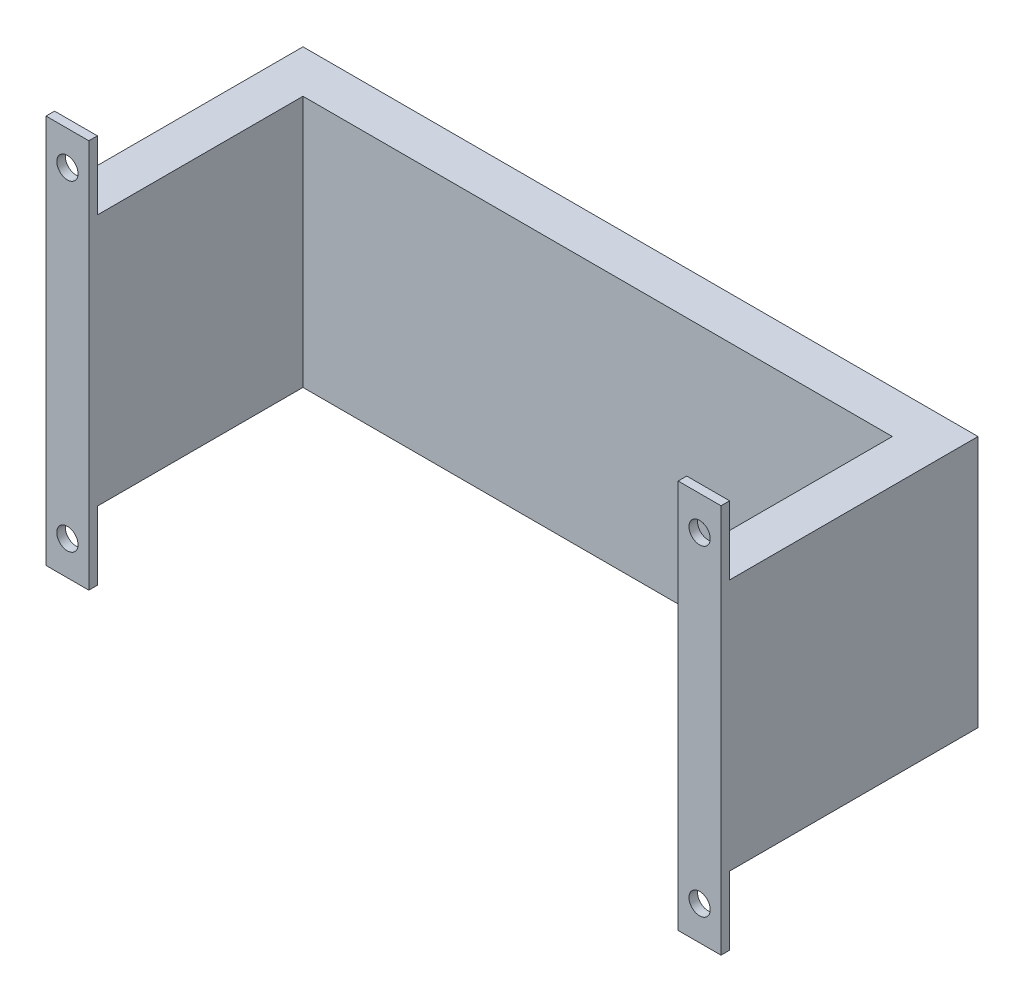
SolidWorks part; units mm, degrees
material "1060 Alloy"
ref_plane "Front Plane" through (0, 0, 0) normal (0, 0, 1) x (1, 0, 0)
ref_plane "Top Plane" through (0, 0, 0) normal (0, 1, 0) x (1, 0, 0)
ref_plane "Right Plane" through (0, 0, 0) normal (1, 0, 0) x (0, 0, -1)
sketch "Sketch1" plane through (0, 0, 0) normal (0, 0, 1) x (1, 0, 0)
  line L1 (125.095, -46.736) -> (-125.095, -46.736)
  line L2 (125.095, -46.736) -> (125.095, 46.736)
  line L3 (125.095, 46.736) -> (-125.095, 46.736)
  line L4 (-125.095, -46.736) -> (-125.095, 46.736)
  line L5 (125.095, -46.736) -> (-125.095, 46.736) construction
  line L6 (125.095, 46.736) -> (-125.095, -46.736) construction
  point P0 (0, 0)
  dimension "D1" = 93.472
  dimension "D2" = 250.19
extrude "Boss-Extrude1" add sketch "Sketch1" along normal blind 95.25
sketch "Sketch5" plane through (0, 0, 95.25) normal (0, 0, 1) x (1, 0, 0)
  line L1 (109.22, -46.736) -> (-109.22, -46.736)
  line L2 (109.22, -46.736) -> (109.22, 46.736)
  line L3 (109.22, 46.736) -> (-109.22, 46.736)
  line L4 (-109.22, -46.736) -> (-109.22, 46.736)
  line L5 (109.22, -46.736) -> (-109.22, 46.736) construction
  line L6 (109.22, 46.736) -> (-109.22, -46.736) construction
  point P0 (0, 0)
  dimension "D1" = 93.472
  dimension "D2" = 218.44
extrude "Cut-Extrude1" cut sketch "Sketch5" against normal blind 79.375
sketch "Sketch6" plane through (0, 0, 95.25) normal (0, 0, 1) x (1, 0, 0)
  line L1 (109.22, 72.136) -> (125.095, 72.136)
  line L2 (109.22, 72.136) -> (109.22, 46.736)
  line L3 (109.22, 46.736) -> (125.095, 46.736)
  line L4 (125.095, 72.136) -> (125.095, 46.736)
  line L5 (109.22, 72.136) -> (125.095, 46.736) construction
  line L6 (109.22, 46.736) -> (125.095, 72.136) construction
  line L8 (125.095, 46.736) -> (109.22, 46.736) construction
  line L9 (125.095, -46.736) -> (125.095, 46.736) construction
  line L11 (0, -51.4096) -> (0, 51.4096) construction
  line L12 (-109.22, 46.736) -> (-125.095, 46.736)
  line L13 (-125.095, 72.136) -> (-125.095, 46.736)
  line L14 (-109.22, 72.136) -> (-125.095, 72.136)
  line L15 (-109.22, 72.136) -> (-109.22, 46.736)
  line L16 (52.3875, 0) -> (-52.3875, 0) construction
  line L17 (109.22, -46.736) -> (125.095, -46.736)
  line L18 (125.095, -72.136) -> (125.095, -46.736)
  line L19 (109.22, -72.136) -> (125.095, -72.136)
  line L20 (109.22, -72.136) -> (109.22, -46.736)
  line L21 (-109.22, -72.136) -> (-109.22, -46.736)
  line L22 (-109.22, -72.136) -> (-125.095, -72.136)
  line L23 (-125.095, -72.136) -> (-125.095, -46.736)
  line L24 (-109.22, -46.736) -> (-125.095, -46.736)
  point P0 (117.1575, 59.436)
  dimension "D1" = 15.875
  dimension "D4" = 25.4
extrude "Boss-Extrude2" add sketch "Sketch6" against normal blind 3.175
sketch "Sketch7" plane through (0, 0, 92.075) normal (0, 0, -1) x (-1, 0, 0)
  line L0 (-125.095, 46.736) -> (125.095, 46.736) construction
  line L3 (117.1575, 59.5376) -> (-145.6767, 59.5376) construction
  line L6 (0, 52.3875) -> (0, -52.3875) construction
  line L7 (52.3875, 0) -> (-52.3875, 0) construction
  line L8 (0, 59.5376) -> (0, -87.3111) construction
  line L9 (-117.1575, -59.5376) -> (117.1575, -59.5376) construction
  circle A0 centre (117.1575, 59.5376) radius 3.937
  circle A1 centre (-117.1575, 59.5376) radius 3.937
  circle A2 centre (117.1575, -59.5376) radius 3.937
  circle A3 centre (-117.1575, -59.5376) radius 3.937
  dimension "D1" = 7.874
  dimension "D2" = 12.8016
  dimension "D3" = 117.1575
extrude "Cut-Extrude2" cut sketch "Sketch7" against normal through all
equation "\"Height\"=3.68"
equation "\"D1@Sketch1\"=\"Height\""
equation "\"D1@Sketch5\"=\"Height\""
